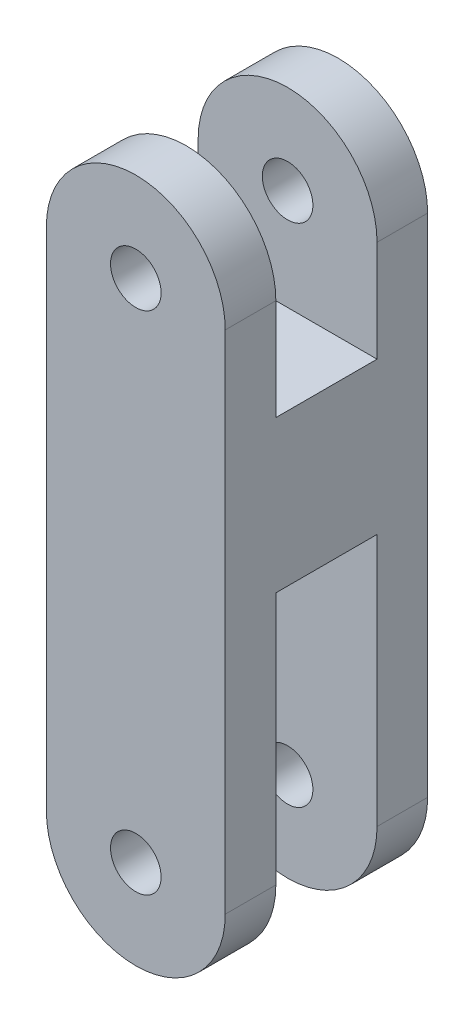
SolidWorks part; units mm, degrees
material "ABS"
ref_plane "Front Plane" through (0, 0, 0) normal (0, 0, 1) x (1, 0, 0)
ref_plane "Top Plane" through (0, 0, 0) normal (0, 1, 0) x (1, 0, 0)
ref_plane "Right Plane" through (0, 0, 0) normal (1, 0, 0) x (0, 0, -1)
sketch "Sketch2" plane through (0, 0, 0) normal (0, 0, 1) x (1, 0, 0)
  line L0 (-35.3553, -70) -> (-35.3553, -270)
  line L1 (35.3553, -270) -> (35.3553, -70)
  arc A0 (35.3553, -70) -> (-35.3553, -70) centre (0, -70) ccw
  arc A1 (-35.3553, -270) -> (35.3553, -270) centre (0, -270) ccw
  circle A2 centre (0, -70) radius 10
  circle A4 centre (0, -270) radius 10
  dimension "D1" = 200
extrude "Boss-Extrude2" add sketch "Sketch2" along normal blind 40 and the other way blind 40
sketch "Sketch3" plane through (0, 0, 0) normal (0, 0, 1) x (1, 0, 0)
  line L0 (-35.3553, -230) -> (35.3553, -230)
  line L1 (35.3553, -270) -> (35.3553, -70) construction
  line L2 (-35.3553, -70) -> (-35.3553, -270) construction
  line L3 (-35.3553, -270) -> (-35.3553, -230)
  line L4 (35.3553, -230) -> (35.3553, -270)
  line L5 (-35.3553, -170) -> (35.3553, -170) construction
  line L6 (35.3553, -110) -> (35.3553, -70)
  line L7 (-35.3553, -70) -> (-35.3553, -110)
  line L8 (-35.3553, -110) -> (35.3553, -110)
  arc A0 (-35.3553, -270) -> (35.3553, -270) centre (0, -270) ccw
  arc A1 (-35.3553, -270) -> (35.3553, -270) centre (0, -270) ccw construction
  arc A2 (-35.3553, -70) -> (35.3553, -70) centre (0, -70) cw
  dimension "D1" = 40
extrude "Cut-Extrude1" cut sketch "Sketch3" against normal blind 20 and the other way blind 20
ref_point "Point1"
ref_point "Point2"
sketch3d "3DSketch2"
  line L0 (0, -170, 40) -> (0, -170, -40)
  point P4 (0, -170, 0)
sketch "Sketch4" plane through (0, 0, 0) normal (0, 0, 1) x (1, 0, 0)
  line L0 (35.3553, -230) -> (-35.3553, -230) construction
  line L1 (-35.3553, -230) -> (35.3553, -230)
  line L2 (-35.3553, -230) -> (-35.3553, -170)
  line L3 (-35.3553, -170) -> (35.3553, -170)
  line L4 (35.3553, -230) -> (35.3553, -170)
  line L5 (-35.3553, -70) -> (-35.3553, -270) construction
  line L6 (35.3553, -270) -> (35.3553, -70) construction
extrude "Cut-Extrude2" cut sketch "Sketch4" against normal up to surface and the other way up to surface up to face at (0, -258.8388, -20) other way up to face at (0, -258.8388, 20)
shell "Shell1" thickness 5
ref_axis "Axis1" through (0, -70, 20) along (0, 0, 1)
ref_point "Point3"
